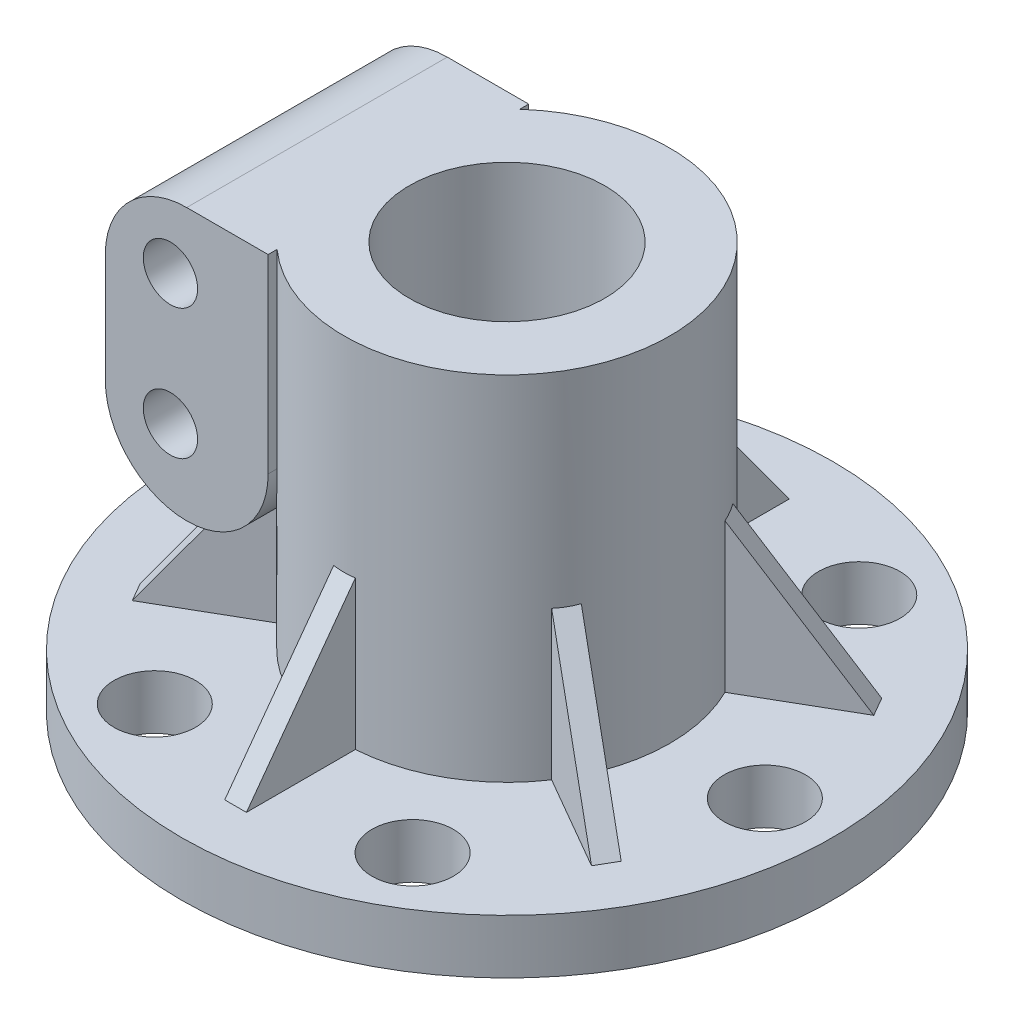
SolidWorks part; units mm, degrees
ref_plane "Front Plane" through (0, 0, 0) normal (0, 0, 1) x (1, 0, 0)
ref_plane "Top Plane" through (0, 0, 0) normal (0, 1, 0) x (1, 0, 0)
ref_plane "Right Plane" through (0, 0, 0) normal (1, 0, 0) x (0, 0, -1)
sketch "Sketch1" plane through (0, 0, 0) normal (0, 0, 1) x (1, 0, 0)
  line L0 (12, 0) -> (12, 10)
  line L1 (12, 10) -> (13, 10)
  line L2 (13, 10) -> (18, 20)
  line L3 (18, 20) -> (18, 75)
  line L4 (18, 75) -> (30, 75)
  line L7 (0, 0) -> (0, 67.6221) construction
  line L8 (30, 75) -> (30, 10)
  line L9 (30, 10) -> (60, 10)
  line L10 (60, 10) -> (60, 0)
  line L11 (12, 0) -> (60, 0)
  point P14 (1.4953, 25.9873)
  dimension "D1" = 60
  dimension "D2" = 10
  dimension "D3" = 12
  dimension "D4" = 13
  dimension "D5" = 18
  dimension "D6" = 30
  dimension "D7" = 20
  dimension "D8" = 75
revolve "Revolve1" add sketch "Sketch1" angle 360 about L7
ref_plane "Plane1" through (0, 0, 24) normal (0, 0, 1) x (1, 0, 0)
sketch "Sketch2" plane through (0, 0, 24) normal (0, 0, 1) x (1, 0, 0)
  line L0 (-35, 60) -> (-35, 40) construction
  line L1 (-20, 60) -> (-20, 40)
  line L2 (-50, 60) -> (-50, 40)
  line L5 (18, 75) -> (-18, 75) construction
  line L7 (30, 75) -> (-30, 75) construction
  line L8 (-20, 75) -> (-20, 60)
  line L9 (-35, 75) -> (-20, 75)
  arc A0 (-35, 75) -> (-50, 60) centre (-35, 60) ccw
  arc A1 (-50, 40) -> (-20, 40) centre (-35, 40) ccw
  point P2 (-35, 50)
  point P15 (-20, 60)
  dimension "D1" = 15
  dimension "D4" = 15
  dimension "D2" = 20
  dimension "D3" = 35
extrude "Boss-Extrude1" add sketch "Sketch2" against normal blind 48
hole_wizard "Hole1" positions "Sketch3" profile "Sketch4" legacy end condition through all
sketch "Sketch3" plane through (0, 0, 24) normal (0, 0, 1) x (1, 0, 0)
  line L0 (-50, 60) -> (-50, 40) construction
  line L1 (-20, 75) -> (-35, 75) construction
  point P8 (-38, 63)
  point P10 (-38, 39)
  point P17 (-38, 39)
  dimension "D1" = 24
  dimension "D2" = 12
  dimension "D3" = 12
sketch "Sketch4" plane through (-38, 63, 24) normal (1, 0, 0) x (0, -1, 0)
  line L0 (0, 0) -> (0, 84)
  line L1 (0, 84) -> (5, 84)
  line L2 (5, 84) -> (5, 0)
  line L3 (5, 0) -> (0, 0)
  line L4 (0, 110) -> (0, -10) construction
  dimension "Diameter" = 10
  dimension "Depth" = 84
sketch "Sketch5" plane through (0, 0, 0) normal (1, 0, 0) x (0, 0, -1)
  line L0 (28, 40) -> (50, 10)
  line L2 (60, 10) -> (-60, 10) construction
  line L3 (50, 10) -> (28, 10)
  line L4 (28, 10) -> (28, 40)
  line L5 (30, 75) -> (-30, 75) construction
  dimension "D1" = 28
  dimension "D2" = 35
  dimension "D3" = 50
extrude "Boss-Extrude2" add sketch "Sketch5" along normal mid plane 4
pattern_circular "CirPattern1" count 6 over 360 about axis through (0, 0, 0) along (0, -1, 0) of "Boss-Extrude2" reverse direction yes
hole_wizard "Hole2" positions "Sketch6" profile "Sketch7" legacy end condition through all
sketch "Sketch6" plane through (0, 10, 0) normal (0, 1, 0) x (1, 0, 0)
  point P0 (47.5, 0)
  point P4 (0, 0)
  dimension "D1" = 47.5
sketch "Sketch7" plane through (47.5, 10, 0) normal (1, 0, 0) x (0, 0, 1)
  line L0 (0, 0) -> (0, 10)
  line L1 (0, 10) -> (7.5, 10)
  line L2 (7.5, 10) -> (7.5, 0)
  line L3 (7.5, 0) -> (0, 0)
  line L4 (0, 110) -> (0, -10) construction
  dimension "Diameter" = 15
  dimension "Depth" = 10
pattern_circular "CirPattern2" count 6 over 360 about axis through (0, 0, 0) along (0, -1, 0) of "Hole2" reverse direction yes
